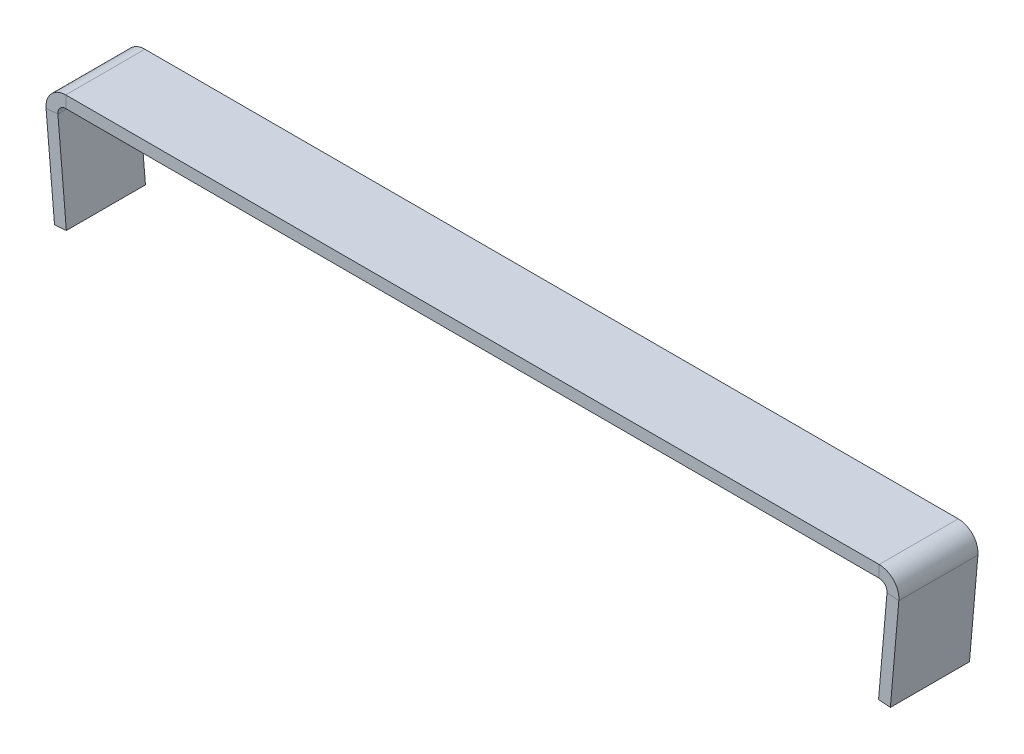
SolidWorks part; units mm, degrees
note: The reader was unsure of these and kept them because the rebuilt part matched: flange length of "Edge-Flange1".
ref_plane "Front Plane" through (0, 0, 0) normal (0, 0, 1) x (1, 0, 0)
ref_plane "Top Plane" through (0, 0, 0) normal (0, 1, 0) x (1, 0, 0)
ref_plane "Right Plane" through (0, 0, 0) normal (1, 0, 0) x (0, 0, -1)
sketch "Sketch1" plane through (0, 0, 0) normal (0, 1, 0) x (1, 0, 0)
  line L1 (-105, -10) -> (105, -10)
  line L2 (-105, -10) -> (-105, 10)
  line L3 (-105, 10) -> (105, 10)
  line L4 (105, -10) -> (105, 10)
  line L5 (-105, -10) -> (105, 10) construction
  line L6 (-105, 10) -> (105, -10) construction
  point P0 (0, 0)
base flange "Base-Flange1" sketch "Sketch1" thickness 3 reverse thickness direction no parameters "D1"=2
edge flange "Edge-Flange1" sketch "Sketch10" flange profiles "Sketch10", "Sketch11" flange angle 85 flange length 30 flange position material outside bend radius 2 thickness 3 relief rectangular parameters "D6"=10, "D8"=1
sketch "Sketch10" plane through (-105, -3, 0) normal (-0.9962, -0.0872, 0) x (0, 0, -1)
  line L0 (10, 0) -> (-10, 0) construction
  line L1 (10, 0) -> (-10, 0)
  line L2 (-10, 0) -> (-10, 26.7261)
  line L3 (-10, 26.7261) -> (10, 26.7261)
  line L4 (10, 26.7261) -> (10, 0)
sketch "Sketch11" plane through (105, -3, 0) normal (0.9962, -0.0872, 0) x (0, 0, 1)
  line L0 (10, 0) -> (-10, 0) construction
  line L1 (10, 0) -> (-10, 0)
  line L2 (-10, 0) -> (-10, 26.7261)
  line L3 (-10, 26.7261) -> (10, 26.7261)
  line L4 (10, 26.7261) -> (10, 0)
bend "EdgeBend1" bend radius 2 bend angle 95 parameters "D5"=1
bend "EdgeBend2" bend radius 2 bend angle 95 parameters "D5"=2
sketch "Bend-Lines1" [suppressed] plane through (0, 0, 0) normal (0, 1, 0) x (1, 0, 0)
sketch "Bounding-Box1" [suppressed] plane through (0, 0, 0) normal (0, 1, 0) x (1, 0, 0)
sheet metal parameters "Sheet-Metal1" thickness 3 parameters "D1"=2
flat pattern "Flat-Pattern1" [suppressed]
sketch "Bend-Lines2" plane through (0, 0, 0) normal (0, 1, 0) x (1, 0, 0)
sketch3d "Bounding-Box2" [suppressed]
  line L0 (-105, 10, 0) -> (105, 10, 0) construction
  line L1 (-105, -10, 0) -> (105, -10, 0) construction
  line L2 (-105, 10, 0) -> (-105, -10, 0) construction
  line L3 (105, 10, 0) -> (105, -10, 0) construction
sheet metal parameters "Sheet-Metal2" thickness 3 parameters "D1"=2
flat pattern "Flat-Pattern1"
sketch "Bend-Lines2" plane through (0, 0, 0) normal (0, 1, 0) x (1, 0, 0)
  line L0 (105.719, -10) -> (105.719, 10) construction
  line L1 (-105.719, 10) -> (-105.719, -10) construction
  line L2 (105.719, -10) -> (105.719, 10) construction
  line L3 (-105.719, 10) -> (-105.719, -10) construction
sketch3d "Bounding-Box2" [suppressed]
  line L0 (133.1641, 10, 0) -> (-133.1641, 10, 0) construction
  line L1 (133.1641, -10, 0) -> (-133.1641, -10, 0) construction
  line L2 (133.1641, 10, 0) -> (133.1641, -10, 0) construction
  line L3 (-133.1641, 10, 0) -> (-133.1641, -10, 0) construction
bend of the flat pattern "Flatten-<EdgeBend1>1"
bend of the flat pattern "Flatten-<EdgeBend2>1"
